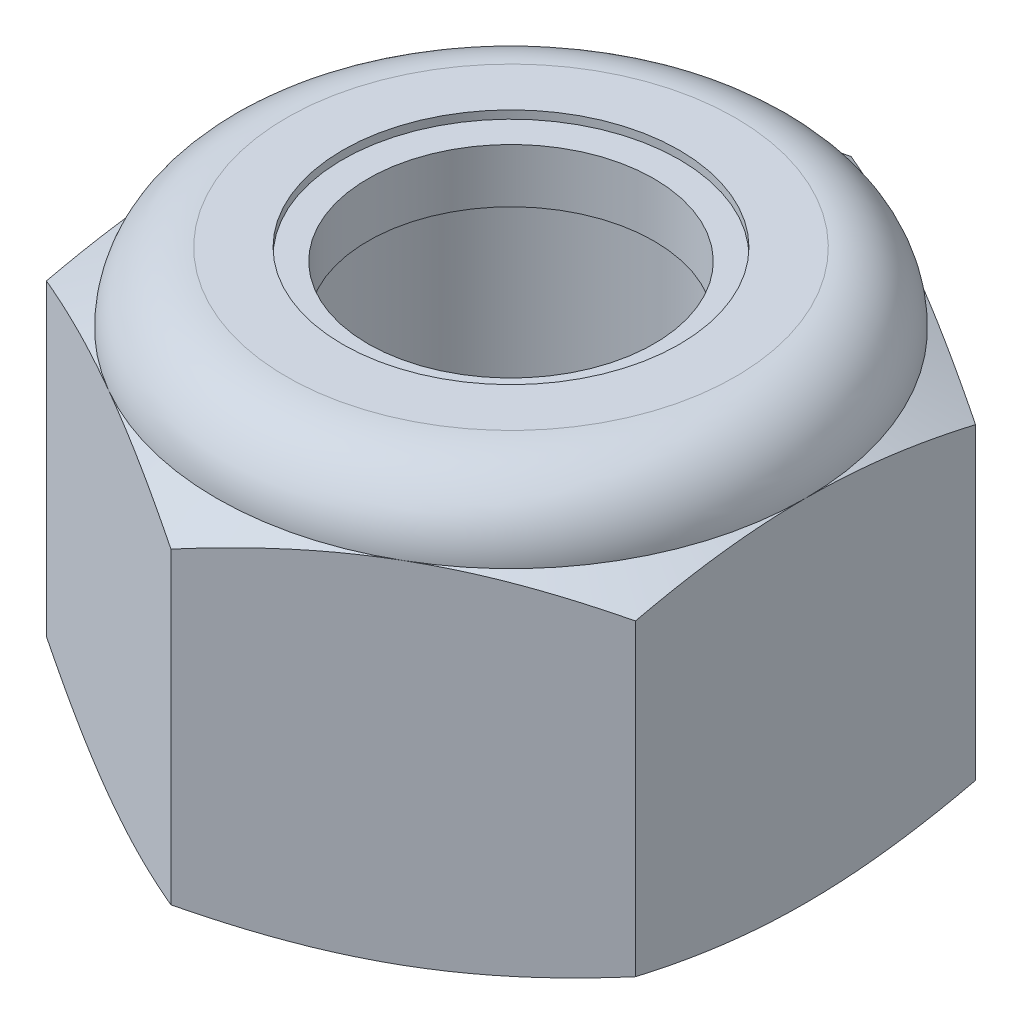
SolidWorks part; units mm, degrees
material "Alloy Steel"
ref_plane "Front" through (0, 0, 0) normal (0, 0, 1) x (1, 0, 0)
ref_plane "Top" through (0, 0, 0) normal (0, 1, 0) x (1, 0, 0)
ref_plane "Right" through (0, 0, 0) normal (1, 0, 0) x (0, 0, -1)
sketch "Sketch1" plane through (0, 0, 0) normal (1, 0, 0) x (0, 0, -1)
  line L0 (0, 0) -> (0, 7.9375) construction
  line L1 (5.5562, 0) -> (-5.5562, 0) construction
  line L2 (-3.175, 7.9375) -> (3.175, 7.9375) construction
  line L3 (3.175, 7.9375) -> (3.175, 7.0304) construction
  point P9 (-3.175, 7.9375)
  point P10 (3.175, 7.9375)
  point P11 (5.5562, 0)
  dimension "Height" = 7.9375
  dimension "Hex Flats" = 11.1125
  dimension "Thread Dia" = 6.35
  dimension "Thread Pitch" = 0.9071
sketch "Sketch13" plane through (0, 0, 0) normal (0, 1, 0) x (1, 0, 0)
  line L1 (0, 6.4158) -> (-5.5563, 3.2079)
  line L2 (-5.5563, 3.2079) -> (-5.5562, -3.2079)
  line L3 (-5.5562, -3.2079) -> (0, -6.4158)
  line L4 (0, -6.4158) -> (5.5563, -3.2079)
  line L5 (5.5563, -3.2079) -> (5.5563, 3.2079)
  line L6 (5.5563, 3.2079) -> (0, 6.4158)
  circle A0 centre (0, 0) radius 5.5562 construction
  circle A1 centre (0, 0) radius 3.175
  point P11 (0, -3.175)
  point P13 (0, 3.175)
extrude "Extrude1" add sketch "Sketch13" along normal up to vertex (7.9375 mm away) up to point (0, 7.9375, 0)
sketch "Sketch5" plane through (0, 0, 0) normal (1, 0, 0) x (0, 0, -1)
  line L0 (0, 0) -> (5.5562, 0)
  line L1 (5.5562, 0) -> (6.4158, 0.4008)
  line L2 (6.4158, 0.4008) -> (6.4158, 6.2138)
  line L3 (6.4158, 6.2138) -> (5.5562, 6.6146)
  line L4 (4.2333, 7.9375) -> (4.2333, 9.2075)
  line L5 (4.2333, 9.2075) -> (7.6858, 9.2075)
  line L6 (7.6858, 9.2075) -> (7.6858, -1.27)
  line L7 (7.6858, -1.27) -> (0, -1.27)
  line L8 (0, -1.27) -> (0, 0)
  line L9 (5.5562, 6.6146) -> (5.5562, 0) construction
  line L12 (6.4158, 7.9375) -> (6.4158, 0) construction
  line L13 (6.4158, 3.9688) -> (7.6858, 3.9688) construction
  line L15 (0, 0) -> (0, 9.2075) construction
  line L18 (5.5562, 0) -> (-5.5562, 0) construction
  line L19 (3.2079, 7.9375) -> (6.4158, 7.9375) construction
  line L20 (0, 9.2075) -> (4.2333, 9.2075) construction
  line L21 (3.2079, 0) -> (6.4158, 0) construction
  arc A0 (5.5562, 6.6146) -> (4.2333, 7.9375) centre (4.2333, 6.6146) ccw
  dimension "D1" = 25
  dimension "D2" = 1.27
  dimension "D4" = 1.3229
revolve "Cut-Revolve3" cut sketch "Sketch5" angle 360 about L15
sketch "Sketch4" plane through (0, 0, 0) normal (1, 0, 0) x (0, 0, -1)
  line L0 (0, 6.6146) -> (3.4925, 6.6146)
  line L1 (3.4925, 6.6146) -> (0, 4.986)
  line L3 (0, 1.6286) -> (3.4925, 0)
  line L4 (3.4925, 0) -> (0, 0)
  line L5 (0, 0) -> (0, 6.6146) construction
  line L10 (0, 0) -> (0, 7.9375) construction
  line L11 (0, 1.6286) -> (0, 0)
  line L12 (0, 6.6146) -> (0, 4.986)
  line L13 (4.8119, 6.6146) -> (0, 6.6146) construction
  dimension "D1" = 25
  dimension "D2" = 6.985
sketch "Sketch6" plane through (0, 0, 0) normal (1, 0, 0) x (0, 0, -1)
  line L0 (0, 6.6146) -> (5.4039, 6.6146)
  line L1 (4.2333, 7.7851) -> (2.1167, 7.7851)
  line L2 (0, 9.2075) -> (0, 6.6146)
  line L3 (2.1167, 9.2075) -> (0, 9.2075)
  line L4 (0, 9.2075) -> (4.2333, 9.2075) construction
  line L5 (0, 0) -> (0, 9.2075) construction
  line L6 (0, 9.2075) -> (0, 0) construction
  line L7 (2.1167, 7.7851) -> (2.1167, 9.2075)
  line L8 (4.2333, 7.9375) -> (4.2333, 7.7851) construction
  line L9 (2.1167, 7.7851) -> (0, 7.7851) construction
  line L10 (0, 7.7851) -> (0, 4.986) construction
  arc A0 (5.4039, 6.6146) -> (4.2333, 7.7851) centre (4.2333, 6.6146) ccw
  arc A1 (5.5562, 6.6146) -> (4.2333, 7.9375) centre (4.2333, 6.6146) ccw construction
  dimension "D1" = 0.1524
revolve "Cut-Revolve4" cut sketch "Sketch6" angle 360 about L6
revolve "Cut-Revolve2" cut sketch "Sketch4" angle 360 about L5
sketch "Sketch7" plane through (0, 0, 0) normal (1, 0, 0) x (0, 0, -1)
  line L0 (2.6988, 6.6908) -> (5.325, 6.6908)
  line L1 (4.2333, 7.7089) -> (2.6988, 7.7089)
  line L2 (2.6988, 7.7089) -> (2.6988, 6.6908)
  line L3 (2.6988, 6.6908) -> (0, 6.6908) construction
  line L4 (0, 6.6908) -> (0, 7.7089) construction
  line L5 (0, 7.7089) -> (2.6988, 7.7089) construction
  line L6 (2.6988, 6.6908) -> (2.6988, 6.6146) construction
  line L7 (0, 6.6146) -> (5.4039, 6.6146) construction
  line L8 (4.2333, 7.7089) -> (4.2333, 7.7851) construction
  arc A0 (5.325, 6.6908) -> (4.2333, 7.7089) centre (4.2333, 6.6146) ccw
  arc A2 (5.4039, 6.6146) -> (4.2333, 7.7851) centre (4.2333, 6.6146) ccw construction
  point P15 (2.6988, 7.7089)
  point P18 (-3.466, 7.7089)
  point P19 (3.466, 7.7089)
  dimension "D2" = 5.3975
revolve "Revolve2" add sketch "Sketch7" angle 360 about L4
sketch "Sketch2" [suppressed] plane through (0, 0, 0) normal (1, 0, 0) x (0, 0, -1)
  line L0 (-3.175, 0) -> (-3.175, 6.6146) construction
  line L1 (0, 0) -> (3.175, 0)
  line L2 (0, 0) -> (0, 6.6146)
  line L3 (0, 6.6146) -> (3.175, 6.6146)
  line L4 (3.175, 0) -> (3.175, 6.6146)
  line L6 (4.8119, 6.6146) -> (5.5562, 6.6146) construction
  line L7 (0, -3.175) -> (0, 0) construction
revolve "Revolve1" [suppressed] add sketch "Sketch2" angle 360 about L7
sketch "Sketch9" [suppressed] plane through (0, 0, 0) normal (1, 0, 0) x (0, 0, -1)
  line L0 (3.2732, 7.465) -> (3.2732, 6.5579) construction
  line L1 (3.2732, 6.5579) -> (2.4876, 7.0115) construction
  line L2 (2.4876, 7.0115) -> (3.2732, 7.465) construction
  line L3 (2.5858, 7.0682) -> (2.5858, 6.9548) construction
  line L4 (3.175, 7.4083) -> (3.175, 6.6146) construction
  line L5 (2.4876, 7.0115) -> (2.5858, 7.0115) construction
  line L6 (3.175, 7.0115) -> (3.2732, 7.0115) construction
  line L7 (3.2241, 7.0115) -> (3.2241, 7.4367) construction
  line L8 (3.2732, 6.5579) -> (3.2241, 7.4367)
  line L9 (3.2241, 7.4367) -> (2.5858, 7.0682)
  line L10 (2.5858, 7.0682) -> (2.5858, 6.9548)
  line L11 (2.5858, 6.9548) -> (3.2732, 6.5579)
  dimension "D1" = 0.9071
sketch "Sketch10" [suppressed] plane through (0, 6.6146, 0) normal (0, 1, 0) x (1, 0, 0)
  circle A1 centre (0, 0) radius 3.175
  circle A2 centre (0, 0) radius 3.175
  dimension "D1" = 0
curve "Helix/Spiral1" [suppressed] pitch 0.9071 height 8.8446 turns 9.75
sweep "Cut-Sweep1" [suppressed] cut profiles "Sketch9" path "Helix/Spiral1"
sketch "Sketch11" [suppressed] plane through (0, 0, 0) normal (1, 0, 0) x (0, 0, -1)
  line L0 (0, 0) -> (0, 7.9375) construction
  line L1 (5.5562, 0) -> (-5.5562, 0) construction
  line L4 (0, 7.9375) -> (0, 0) construction
  line L5 (0, 3.9688) -> (3.175, 3.9688) construction
  line L6 (0, 0) -> (3.4925, 0)
  line L7 (0, 1.6286) -> (0, 0)
  line L8 (3.4925, 0) -> (0, 1.6286)
  dimension "D1" = 6.985
  dimension "D2" = 25
revolve "Revolve3" [suppressed] add sketch "Sketch11" angle 360 about L4
sketch "Sketch12" [suppressed] plane through (0, 0, 0) normal (1, 0, 0) x (0, 0, -1)
  line L0 (3.4925, 6.6146) -> (0, 6.6146)
  line L1 (0, 6.6146) -> (0, 0)
  line L2 (0, 0) -> (3.4925, 0)
  line L3 (5.5562, 0) -> (-5.5562, 0) construction
  line L4 (3.4925, 0) -> (3.4925, 6.6146)
  line L5 (-3.4925, 0) -> (3.4925, 0) construction
revolve "Revolve4" [suppressed] add sketch "Sketch12" angle 360 about L0
combine bodies "Combine1" [suppressed] operation type subtract main body 136 bodies to subtract 133
equation "\"D4@Sketch5\" = \"Height@Sketch1\" / 6"
equation "\"D1@Sketch9\" = \"Thread Pitch@Sketch1\""
equation "\"D2@Sketch9\" = \"Thread Pitch@Sketch1\" / 8"
equation "\"D4@Helix/Spiral1\" = \"Thread Pitch@Sketch1\""
equation "\"D3@Helix/Spiral1\" = \"Thread Pitch@Sketch1\" + \"Height@Sketch1\""
equation "\"D2@Sketch4\" = \"Thread Dia@Sketch1\" * 1.1"
equation "\"D1@Sketch11\" = \"Thread Dia@Sketch1\" * 1.1"
equation "\"D2@Sketch7\" = \"Thread Dia@Sketch1\" * .85"
